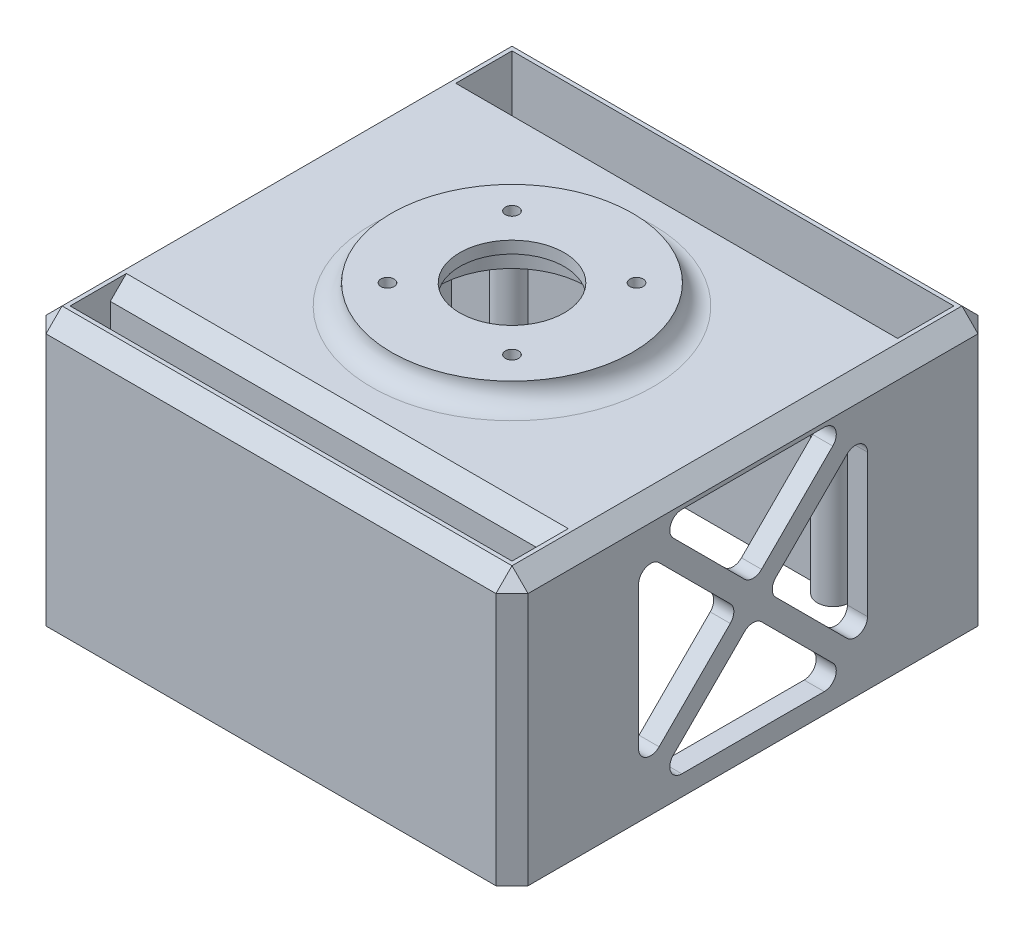
SolidWorks part; units mm, degrees
ref_plane "前视基准面" through (0, 0, 0) normal (0, 0, 1) x (1, 0, 0)
ref_plane "上视基准面" through (0, 0, 0) normal (0, 1, 0) x (1, 0, 0)
ref_plane "右视基准面" through (0, 0, 0) normal (1, 0, 0) x (0, 0, -1)
other "Configuration Table"
sketch "草图1" plane through (0, 0, 0) normal (0, 1, 0) x (1, 0, 0)
  line L1 (0, 0) -> (120, 0)
  line L2 (0, 0) -> (0, 120)
  line L3 (0, 120) -> (120, 120)
  line L4 (120, 0) -> (120, 120)
  dimension "D1" = 120
  dimension "D2" = 120
extrude "凸台-拉伸1" add sketch "草图1" along normal blind 67
shell "抽壳1" thickness 5 removed face at (60, 0, -60)
sketch "草图3" plane through (0, 67, 0) normal (0, 1, 0) x (1, 0, 0)
  line L0 (0, 60) -> (120, 60) construction
  line L5 (0, 120) -> (0, 0) construction
  line L6 (120, 0) -> (120, 120) construction
  line L7 (60, 120) -> (60, 0) construction
  line L8 (120, 120) -> (0, 120) construction
  line L9 (0, 0) -> (120, 0) construction
  circle A0 centre (60, 60) radius 30
  dimension "D1" = 60
extrude "凸台-拉伸2" add sketch "草图3" along normal blind 5
sketch "草图2" plane through (0, 62, 0) normal (0, -1, 0) x (1, 0, 0)
  line L0 (5, -60) -> (115, -60) construction
  line L1 (5, -115) -> (5, -5) construction
  line L2 (115, -5) -> (115, -115) construction
  line L3 (60, -5) -> (60, -115) construction
  line L4 (5, -5) -> (115, -5) construction
  line L5 (115, -115) -> (5, -115) construction
  circle A0 centre (44.5, -44.5) radius 1.65
  circle A1 centre (44.5, -75.5) radius 1.65
  circle A2 centre (75.5, -44.5) radius 1.65
  circle A3 centre (75.5, -75.5) radius 1.65
  circle A4 centre (60, -60) radius 18.5
  dimension "D1" = 31
  dimension "D2" = 3.3
  dimension "D3" = 31
  dimension "D4" = 37
extrude "切除-拉伸1" cut sketch "草图2" against normal through all
sketch "草图4" plane through (0, 72, 0) normal (0, 1, 0) x (1, 0, 0)
  circle A0 centre (60, 60) radius 18.5
  circle A1 centre (60, 60) radius 13
  circle A2 centre (60, 60) radius 18.5 construction
  dimension "D1" = 26
extrude "凸台-拉伸3" add sketch "草图4" against normal blind 3
fillet "圆角2" radius 5 1 edges at (60, 67, -30)
sketch "草图6" plane through (0, 67, 0) normal (0, 1, 0) x (1, 0, 0)
  line L0 (0, 0) -> (120, 0) construction
  line L1 (5, 5) -> (115, 5)
  line L2 (5, 5) -> (5, 15)
  line L3 (5, 15) -> (115, 15)
  line L4 (115, 5) -> (115, 15)
  line L5 (120, 0) -> (120, 120) construction
  line L6 (0, 120) -> (0, 0) construction
  line L7 (0, 60) -> (120, 60) construction
  line L8 (5, 105) -> (115, 105)
  line L9 (115, 115) -> (115, 105)
  line L10 (5, 115) -> (115, 115)
  line L11 (5, 115) -> (5, 105)
  dimension "D1" = 5
  dimension "D2" = 5
  dimension "D3" = 5
  dimension "D4" = 10
extrude "切除-拉伸2" cut sketch "草图6" against normal up to surface (5 mm away) up to face at (60, 62, -78.5)
sketch "草图8" plane through (0, 62, 0) normal (0, -1, 0) x (1, 0, 0)
  line L0 (115, -15) -> (115, -105) construction
  line L1 (5, -15) -> (115, -15)
  line L2 (5, -15) -> (5, -20)
  line L3 (5, -20) -> (115, -20)
  line L4 (115, -15) -> (115, -20)
  line L5 (115, -5) -> (115, -115) construction
  line L6 (5, -105) -> (115, -105)
  line L7 (5, -105) -> (5, -100)
  line L8 (5, -100) -> (115, -100)
  line L9 (115, -105) -> (115, -100)
  dimension "D1" = 5
  dimension "D2" = 5
extrude "凸台-拉伸4" add sketch "草图8" along normal blind 57
sketch "草图9" plane through (0, 62, 0) normal (0, -1, 0) x (1, 0, 0)
  line L0 (5, -20) -> (115, -20) construction
  line L1 (115, -100) -> (5, -100) construction
  line L2 (115, -100) -> (5, -100) construction
  line L3 (5, -20) -> (115, -20) construction
  line L4 (60, -5) -> (60, -115) construction
  line L5 (5, -5) -> (115, -5) construction
  line L6 (115, -115) -> (5, -115) construction
  circle A0 centre (20, -20) radius 4
  circle A1 centre (20, -100) radius 4
  circle A2 centre (100, -100) radius 4
  circle A3 centre (100, -20) radius 4
  dimension "D1" = 80
  dimension "D2" = 8
extrude "凸台-拉伸5" add sketch "草图9" along normal up to surface (57 mm away) up to face at (60, 5, -102.5)
sketch "草图10" plane through (0, 5, 0) normal (0, -1, 0) x (1, 0, 0)
  line L0 (20, -100) -> (100, -100) construction
  line L1 (20, -100) -> (20, -20) construction
  circle A0 centre (20, -100) radius 1.9
  circle A1 centre (100, -100) radius 1.9
  circle A2 centre (100, -20) radius 1.9
  circle A3 centre (20, -20) radius 1.9
  dimension "D6" = 3.8
  dimension "D3" = 90
  dimension "D4" = 80
  dimension "D5" = 80
  dimension "D1" = 2
  dimension "D2" = 2
extrude "切除-拉伸3" cut sketch "草图10" against normal blind 3.5
sketch "草图12" plane through (120, 0, 0) normal (1, 0, 0) x (0, 0, -1)
  line L0 (20, 5) -> (20, 62) construction
  line L1 (20, 5) -> (20, 62) construction
  line L2 (100, 5) -> (100, 62) construction
  line L3 (100, 5) -> (100, 62) construction
  line L4 (60, 67) -> (60, 0) construction
  line L5 (0, 67) -> (120, 67) construction
  line L6 (0, 0) -> (120, 0) construction
  line L7 (31.5, 58.4645) -> (56.4645, 33.5)
  line L8 (31.5, 62) -> (88.5, 62) construction
  line L9 (31.5, 62) -> (31.5, 5) construction
  line L10 (31.5, 5) -> (88.5, 5) construction
  line L11 (88.5, 62) -> (88.5, 5) construction
  line L12 (56.4645, 33.5) -> (31.5, 8.5355)
  line L13 (31.5, 8.5355) -> (31.5, 58.4645)
  line L14 (88.5, 33.5) -> (31.5, 33.5) construction
  line L15 (35.0355, 62) -> (84.9645, 62)
  line L16 (84.9645, 62) -> (60, 37.0355)
  line L17 (60, 37.0355) -> (35.0355, 62)
  line L18 (88.5, 58.4645) -> (88.5, 8.5355)
  line L19 (88.5, 8.5355) -> (63.5355, 33.5)
  line L20 (63.5355, 33.5) -> (88.5, 58.4645)
  line L21 (84.9645, 5) -> (35.0355, 5)
  line L22 (35.0355, 5) -> (60, 29.9645)
  line L23 (60, 29.9645) -> (84.9645, 5)
  point P20 (60, 33.5)
  point P32 (60, 33.5)
  dimension "D1" = 5
  dimension "D2" = 5
  dimension "D3" = 57
  dimension "D5" = 5
  dimension "D4" = 4
extrude "切除-拉伸4" cut sketch "草图12" against normal through all
fillet "圆角3" radius 3 24 edges at (2.5, 8.5355, -88.5) (117.5, 8.5355, -88.5) (117.5, 33.5, -56.4645) (117.5, 29.9645, -60) (117.5, 33.5, -63.5355) (2.5, 58.4645, -31.5) (2.5, 8.5355, -31.5) (2.5, 5, -35.0355) (2.5, 5, -84.9645) (2.5, 29.9645, -60) (2.5, 33.5, -63.5355) (2.5, 33.5, -56.4645) (2.5, 37.0355, -60) (2.5, 62, -35.0355) (2.5, 58.4645, -88.5) (2.5, 62, -84.9645) (117.5, 58.4645, -88.5) (117.5, 62, -84.9645) (117.5, 37.0355, -60) (117.5, 62, -35.0355) (117.5, 5, -84.9645) (117.5, 5, -35.0355) (117.5, 8.5355, -31.5) (117.5, 58.4645, -31.5)
chamfer "倒角1" distance 4 angle 45 10 edges at (120, 67, -60) (120, 33.5, 0) (60, 67, 0) (0, 33.5, 0) (0, 67, -60) (0, 33.5, -120) (60, 67, -120) (120, 33.5, -120) (60, 67, -105) (60, 67, -15)
chamfer "倒角2" distance 0.5 angle 45 4 edges at (20, 5, -21.9) (20, 5, -101.9) (100, 5, -101.9) (100, 5, -21.9)
ref_plane "基准面1" through (0, 0, -60) normal (0, 0, 1) x (1, 0, 0)
